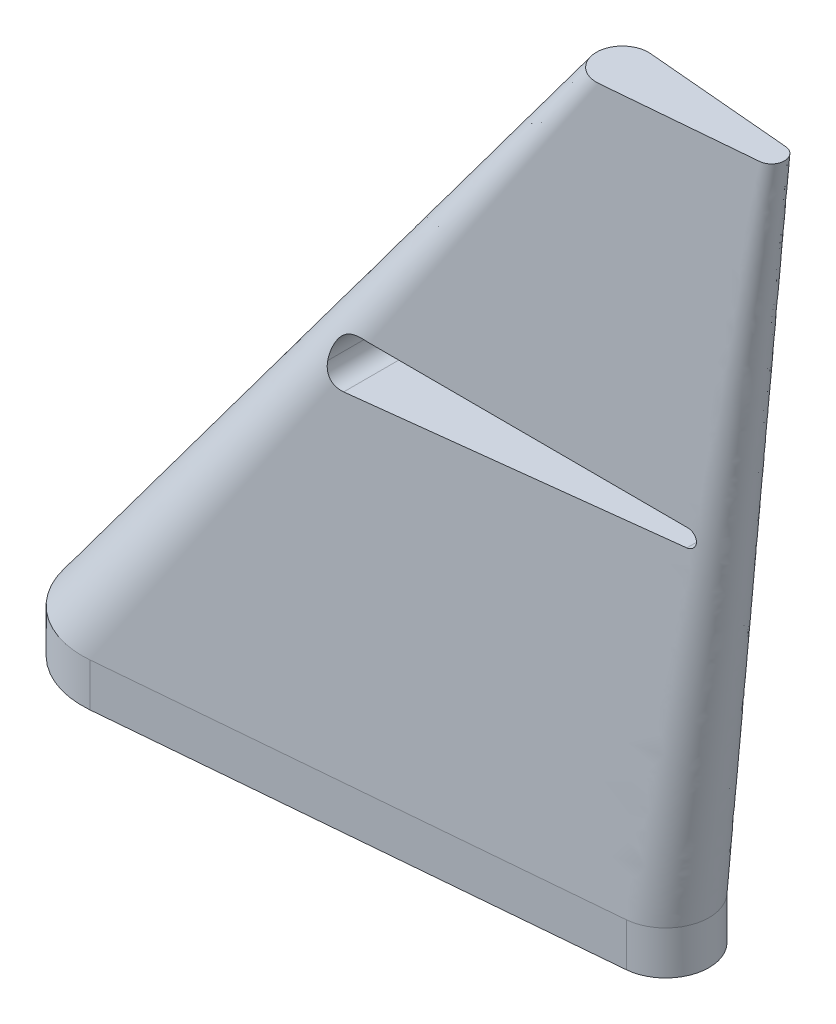
SolidWorks part; units mm, degrees
material "Cast Carbon Steel"
ref_plane "Front Plane" through (0, 0, 0) normal (0, 0, 1) x (1, 0, 0)
ref_plane "Top Plane" through (0, 0, 0) normal (0, 1, 0) x (1, 0, 0)
ref_plane "Right Plane" through (0, 0, 0) normal (1, 0, 0) x (0, 0, -1)
sketch "Sketch1" plane through (0, 0, 0) normal (0, 1, 0) x (1, 0, 0)
  line L0 (2.7614, 2.5303) -> (17.2223, 1.2652)
  line L1 (0, 0) -> (18.3816, 0) construction
  line L2 (0, -2.5303) -> (0, 2.5303) construction
  line L3 (0, 2.5303) -> (2.7614, 2.5303) construction
  line L4 (17.2223, 1.2652) -> (18.3816, 1.2652) construction
  line L5 (18.3816, 1.2652) -> (18.3816, -1.2652) construction
  line L6 (17.2223, -1.2652) -> (18.3816, -1.2652) construction
  line L7 (0, -2.5303) -> (2.7614, -2.5303) construction
  line L8 (2.7614, -2.5303) -> (17.2223, -1.2652)
  arc A0 (2.7614, -2.5303) -> (2.7614, 2.5303) centre (2.54, 0) cw
  arc A1 (17.2223, 1.2652) -> (17.2223, -1.2652) centre (17.1116, 0) cw
  dimension "D1" = 1.27
  dimension "D3" = 2.54
  dimension "D2" = 5
extrude "Boss-Extrude1" add sketch "Sketch1" against normal blind 1.27
ref_plane "Plane2" through (0, 20.32, 0) normal (0, 1, 0) x (1, 0, 0)
sketch "Sketch5" plane through (0, 20.32, 0) normal (0, 1, 0) x (1, 0, 0)
  line L0 (0, 0) -> (18.3816, 0) construction
  line L1 (15.908, 0.7591) -> (20.2463, 0.3796)
  line L2 (20.2463, -0.3796) -> (15.908, -0.7591)
  arc A0 (2.7614, 2.5303) -> (2.7614, -2.5303) centre (2.54, 0) ccw construction
  arc A1 (17.2223, -1.2652) -> (17.2223, 1.2652) centre (17.1116, 0) ccw construction
  arc A2 (20.2463, 0.3796) -> (20.2463, -0.3796) centre (20.2131, 0) cw
  arc A3 (15.908, -0.7591) -> (15.908, 0.7591) centre (15.8416, 0) cw
  dimension "D1" = 0.762
  dimension "D2" = 0.381
  dimension "D3" = 5
  dimension "D4" = 2.54
loft "Loft2" add profiles "Sketch1<3>", "Sketch5" connector at (2.7614, 0, 2.5303) connector at (15.908, 20.32, 0.7591)
sketch "Sketch1<3>" plane through (0, 0, 0) normal (0, 1, 0) x (1, 0, 0) same geometry as "Sketch1"
sketch "Sketch7" plane through (0, 0, 0) normal (0, 0, 1) x (1, 0, 0)
  line L0 (7.5394, 10.16) -> (19.4883, 10.16) construction
  line L1 (18.3823, 0) -> (20.5943, 20.32) construction
  line L2 (15.079, 20.32) -> (-0.0001, 0) construction
  line L3 (9.914, 11.1721) -> (18.5905, 10.413)
  line L4 (18.5754, 9.9061) -> (9.3314, 9.6522)
  line L5 (8.8094, 10.16) -> (8.8094, 8.2865) construction
  arc A0 (8.8094, 10.16) -> (9.914, 11.1721) centre (9.8254, 10.16) cw
  arc A1 (18.5905, 10.413) -> (18.5754, 9.9061) centre (18.5684, 10.16) cw
  arc A2 (9.3314, 9.6522) -> (8.8094, 10.16) centre (9.3174, 10.16) cw
  dimension "D3" = 0.254
  dimension "D4" = 1.016
  dimension "D5" = 0.508
  dimension "D1" = 10.16
  dimension "D2" = 5
  dimension "D6" = 1.778
extrude "Cut-Extrude1" cut sketch "Sketch7" against normal through all both and the other way through all
